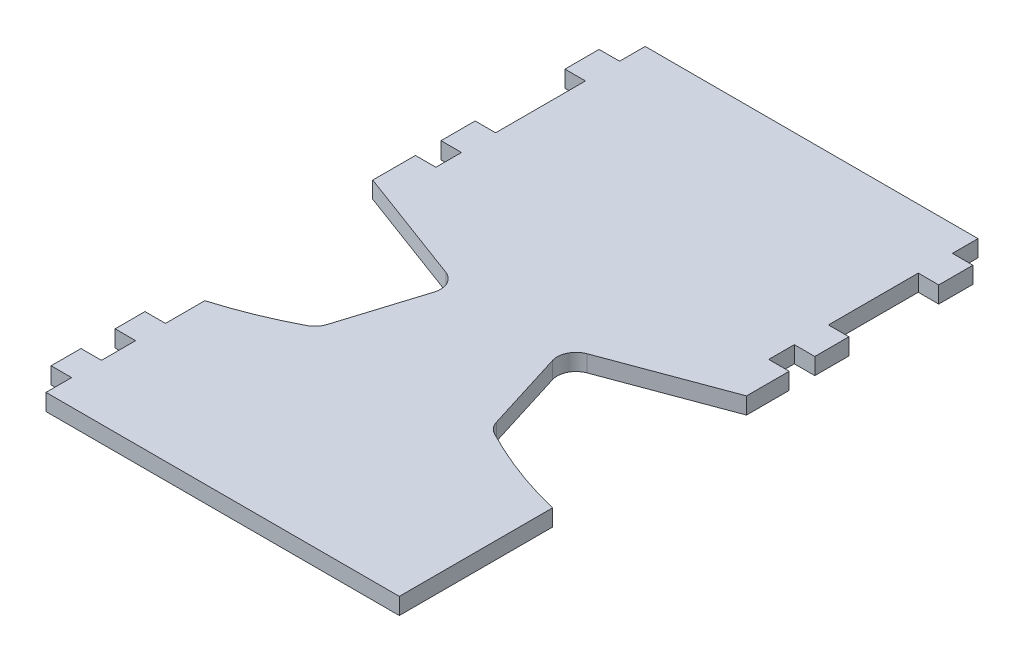
SolidWorks part; units mm, degrees
ref_plane "Front" through (0, 0, 0) normal (0, 0, 1) x (1, 0, 0)
ref_plane "Top" through (0, 0, 0) normal (0, 1, 0) x (1, 0, 0)
ref_plane "Right" through (0, 0, 0) normal (1, 0, 0) x (0, 0, -1)
ref_axis "side-side" through (80.9, 0, 0) along (-1, 0, 0)
ref_axis "up-down" through (0, 50, 0) along (0, -1, 0)
ref_axis "front-back" through (0, 0, -80.9) along (0, 0, 1)
sketch "Sketch1" plane through (0, 0, 0) normal (0, 1, 0) x (1, 0, 0)
  line L0 (0, 45.72) -> (0, 82.7528) construction
  line L1 (-49.53, 45.72) -> (49.53, 45.72)
  line L2 (-55.626, 38.1) -> (-55.626, 27.94)
  line L3 (-49.53, -132.6173) -> (55.626, -132.6173)
  line L4 (55.626, 38.1) -> (55.626, 27.94)
  line L8 (-17.632, -49.0369) -> (-25.1877, -73.287)
  line L9 (-21.0198, -42.1368) -> (-55.626, -29.2719)
  line L10 (-55.626, -97.0573) -> (-55.626, -105.9473)
  line L11 (55.626, -29.2719) -> (21.0198, -42.1368)
  line L12 (17.632, -49.0369) -> (25.1877, -73.287)
  line L13 (55.626, -87.0224) -> (55.626, -132.6173)
  line L14 (55.626, -16.5719) -> (55.626, -29.2719)
  line L15 (-49.53, 38.1) -> (-55.626, 38.1)
  line L16 (-49.53, 38.1) -> (-49.53, 45.72)
  line L17 (-55.626, -16.5719) -> (-55.626, -29.2719)
  line L19 (-49.53, -8.9519) -> (-55.626, -8.9519)
  line L20 (-49.53, -8.9519) -> (-49.53, -16.5719)
  line L21 (-49.53, -16.5719) -> (-55.626, -16.5719)
  line L24 (-49.53, -116.1073) -> (-55.626, -116.1073) construction
  line L25 (55.626, 38.1) -> (49.53, 38.1)
  line L26 (49.53, 45.72) -> (49.53, 38.1)
  line L27 (55.626, -16.5719) -> (49.53, -16.5719)
  line L29 (55.626, -8.9519) -> (49.53, -8.9519)
  line L30 (49.53, -16.5719) -> (49.53, -8.9519)
  line L32 (-49.53, -85.3598) -> (-49.53, -97.0573)
  line L33 (-55.626, -97.0573) -> (-49.53, -97.0573)
  line L36 (-49.53, -132.6173) -> (-49.53, -124.9973)
  line L37 (-55.626, -124.9973) -> (-49.53, -124.9973)
  line L38 (-49.53, -105.9473) -> (-49.53, -116.1073) construction
  line L39 (-55.626, -105.9473) -> (-49.53, -105.9473) construction
  line L40 (-49.53, -116.1073) -> (-55.626, -116.1073)
  line L41 (-49.53, -105.9473) -> (-49.53, -116.1073)
  line L42 (-55.626, -105.9473) -> (-49.53, -105.9473)
  line L43 (-49.53, 1.2081) -> (-55.626, 1.2081) construction
  line L44 (-55.626, 27.94) -> (-49.53, 27.94) construction
  line L45 (-49.53, 27.94) -> (-49.53, 1.2081) construction
  line L46 (-49.53, 1.2081) -> (-55.626, 1.2081)
  line L47 (-55.626, 27.94) -> (-49.53, 27.94)
  line L48 (-49.53, 27.94) -> (-49.53, 1.2081)
  line L49 (-55.626, 1.2081) -> (-55.626, -8.9519)
  line L50 (-55.626, -116.1073) -> (-55.626, -124.9973)
  line L51 (55.626, 1.2081) -> (49.53, 1.2081) construction
  line L52 (49.53, 1.2081) -> (49.53, 27.94) construction
  line L53 (49.53, 27.94) -> (55.626, 27.94) construction
  line L54 (55.626, 1.2081) -> (49.53, 1.2081)
  line L55 (49.53, 1.2081) -> (49.53, 27.94)
  line L56 (49.53, 27.94) -> (55.626, 27.94)
  line L57 (55.626, 1.2081) -> (55.626, -8.9519)
  arc A1 (-17.632, -49.0369) -> (-21.0198, -42.1368) centre (-22.967, -47.3746) ccw
  arc A2 (-27.9391, -76.5796) -> (-25.1877, -73.287) centre (-30.5228, -71.6248) ccw
  arc A3 (-27.9391, -76.5796) -> (-49.53, -85.3598) centre (-85.09, 33.02) cw
  arc A4 (21.0198, -42.1368) -> (17.632, -49.0369) centre (22.967, -47.3746) ccw
  arc A5 (25.1877, -73.287) -> (27.9391, -76.5796) centre (30.5228, -71.6248) ccw
  arc A6 (27.9391, -76.5796) -> (55.626, -87.0224) centre (85.09, 33.02) ccw
extrude "Boss-Extrude1" add sketch "Sketch1" along normal mid plane 4.953
